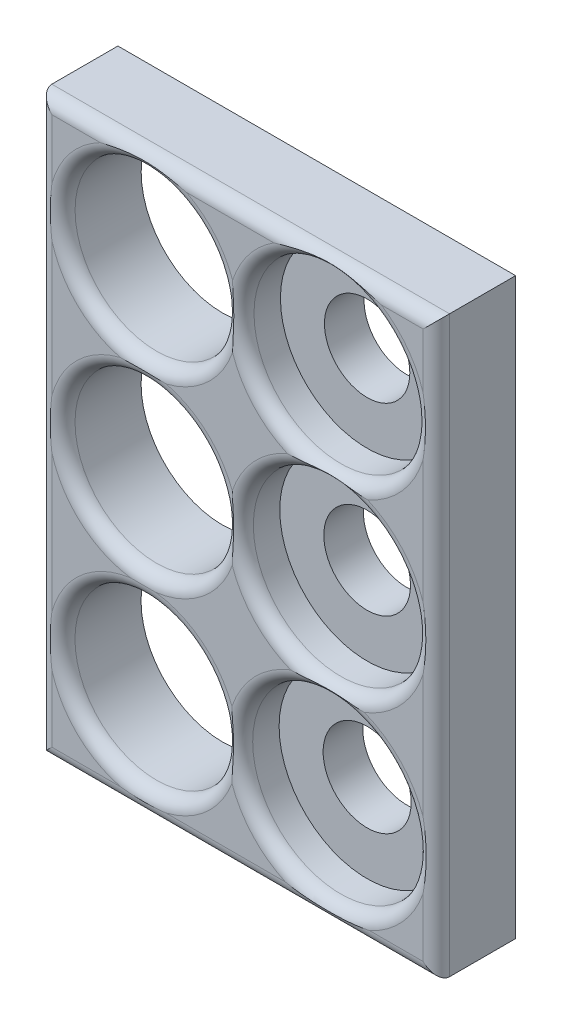
SolidWorks part; units mm, degrees
ref_plane "前视基准面" through (0, 0, 0) normal (0, 0, 1) x (1, 0, 0)
ref_plane "上视基准面" through (0, 0, 0) normal (0, 1, 0) x (1, 0, 0)
ref_plane "右视基准面" through (0, 0, 0) normal (1, 0, 0) x (0, 0, -1)
other "Configuration Table"
sketch "Sketch1" plane through (0, 0, 0) normal (0, 0, 1) x (1, 0, 0)
  line L5 (-18.0373, 16.3217) -> (12.057, 16.3217)
  line L6 (-18.0373, 16.3217) -> (-18.0373, -27.1226)
  line L7 (-18.0373, -27.1226) -> (12.057, -27.1226)
  line L8 (12.057, 16.3217) -> (12.057, -27.1226)
  circle A0 centre (-10.1177, 8.9452) radius 6.16
  circle A1 centre (-10.1177, -4.9479) radius 6.165
  circle A2 centre (-10.1177, -19.1578) radius 6.17
  circle A3 centre (3.8207, 8.9452) radius 3.23
  circle A4 centre (3.8207, 8.9452) radius 6.56
  circle A5 centre (3.8207, -4.9479) radius 3.28
  circle A6 centre (3.8207, -4.9479) radius 6.61
  circle A7 centre (3.8207, -19.1578) radius 3.33
  circle A8 centre (3.8207, -19.1578) radius 6.66
  dimension "D1" = 43.4443
  dimension "D2" = 30.0942
extrude "Boss-Extrude1" add sketch "Sketch1" along normal blind 3 contours L8 L5 L6 L7 A8 A6 A4 A2 A1 A0 region at (-3.4582, -5.7788, 0)
extrude "Boss-Extrude2" add sketch "Sketch1<3>" against normal blind 3 contours L8 L5 L6 L7 A8 A6 A4 A2 A1 A0 | A4 A3 | A6 A5 | A8 A7 region at (-3.4582, -5.7788, 0) region at (-2.5538, 8.9452, 0) region at (-2.6024, -4.9479, 0) region at (-2.651, -19.1578, 0)
sketch "Sketch1<3>" plane through (0, 0, 0) normal (0, 0, 1) x (1, 0, 0) same geometry as "Sketch1"
fillet "Fillet1" radius 1 10 edges at (-2.9901, -27.1226, 3) (-18.0373, -5.4005, 3) (-2.9901, 16.3217, 3) (12.057, -5.4005, 3) (-3.9577, 8.9452, 3) (-3.9527, -4.9479, 3) (-3.9477, -19.1578, 3) (10.3807, 8.9452, 3) (10.4307, -4.9479, 3) (10.4807, -19.1578, 3)
